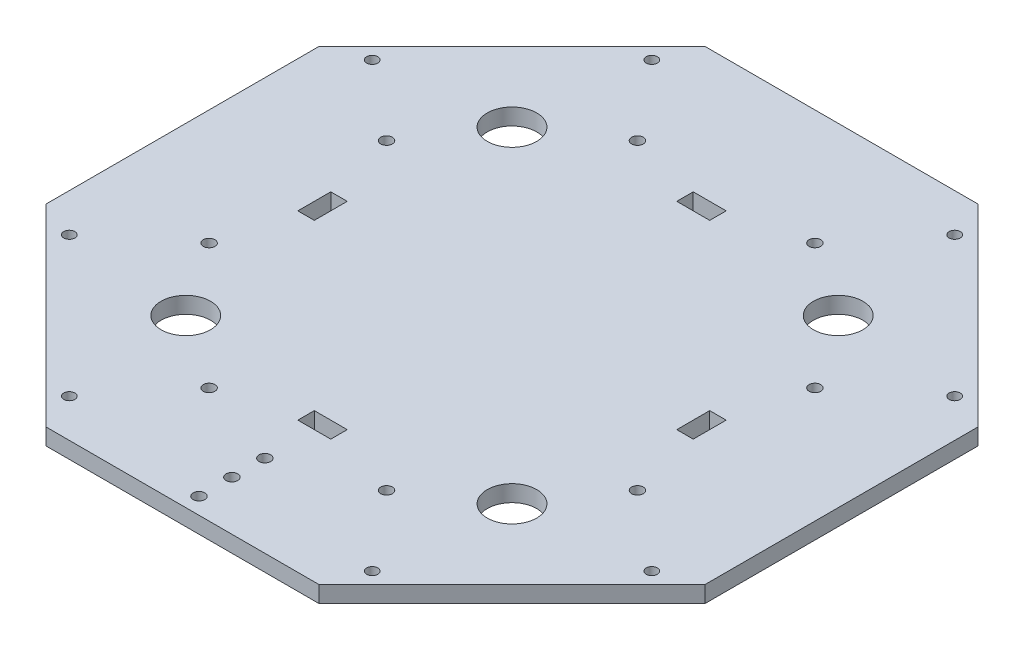
SolidWorks part; units mm, degrees
material "Custom Plastic"
ref_plane "Front Plane" through (0, 0, 0) normal (0, 0, 1) x (1, 0, 0)
ref_plane "Top Plane" through (0, 0, 0) normal (0, 1, 0) x (1, 0, 0)
ref_plane "Right Plane" through (0, 0, 0) normal (1, 0, 0) x (0, 0, -1)
ref_axis "Axis1" through (0, -0.2997, 0) along (0, 1, 0)
sketch "Base sketch" plane through (0, 0, 0) normal (0, 1, 0) x (1, 0, 0)
  line L1 (-127, 52.6051) -> (-127, -52.6051)
  line L2 (-127, -52.6051) -> (-52.6051, -127)
  line L3 (-52.6051, -127) -> (52.6051, -127)
  line L4 (52.6051, -127) -> (127, -52.6051)
  line L5 (127, -52.6051) -> (127, 52.6051)
  line L6 (127, 52.6051) -> (52.6051, 127)
  line L7 (52.6051, 127) -> (-52.6051, 127)
  line L8 (-52.6051, 127) -> (-127, 52.6051)
  circle A0 centre (0, 0) radius 127 construction
  dimension "D1" = 254
extrude "Base" add sketch "Base sketch" along normal blind 6.35
sketch "Sketch3" plane through (0, 6.35, 0) normal (0, 1, 0) x (1, 0, 0)
  line L0 (52.6051, 127) -> (-52.6051, 127) construction
  line L1 (-34.925, 114.3) -> (34.925, 114.3)
  line L2 (-34.925, 114.3) -> (-34.925, 79.375)
  line L4 (-34.925, 79.375) -> (34.925, 79.375)
  line L5 (34.925, 114.3) -> (34.925, 79.375)
  point P6 (0, 79.375)
  dimension "D1" = 69.85
  dimension "D2" = 34.925
  dimension "D3" = 12.7
sketch "Sketch4" plane through (0, 6.35, 0) normal (0, 1, 0) x (1, 0, 0)
  line L0 (0, 0) -> (0, 127) construction
  line L1 (52.6051, 127) -> (-52.6051, 127) construction
  line L4 (-6.35, 69.85) -> (6.35, 69.85)
  line L5 (-6.35, 69.85) -> (-6.35, 76.2)
  line L6 (-6.35, 76.2) -> (6.35, 76.2)
  line L7 (6.35, 69.85) -> (6.35, 76.2)
  line L8 (-6.35, 69.85) -> (6.35, 76.2) construction
  line L10 (-6.35, 76.2) -> (6.35, 69.85) construction
  point P5 (0, 73.025)
  dimension "D1" = 6.35
  dimension "D2" = 12.7
  dimension "D3" = 53.975
extrude "Support cutouts" cut sketch "Sketch4" against normal up to next
pattern_circular "Support cutout pattern" count 4 over 360 about axis through (0, -0.2997, 0) along (0, 1, 0) of "Support cutouts"
sketch "Sketch11" plane through (0, 6.35, 0) normal (0, 1, 0) x (1, 0, 0)
  line L1 (95.25, 39.4538) -> (39.4538, 95.25) construction
  line L2 (39.4538, 95.25) -> (-39.4538, 95.25) construction
  line L3 (-39.4538, 95.25) -> (-95.25, 39.4538) construction
  line L4 (-95.25, 39.4538) -> (-95.25, -39.4538) construction
  line L5 (-95.25, -39.4538) -> (-39.4538, -95.25) construction
  line L6 (-39.4538, -95.25) -> (39.4538, -95.25) construction
  line L7 (39.4538, -95.25) -> (95.25, -39.4538) construction
  line L8 (95.25, -39.4538) -> (95.25, 39.4538) construction
  line L9 (-34.1933, 82.55) -> (-82.55, 34.1933)
  line L10 (-82.55, 34.1933) -> (-82.55, -34.1933)
  line L11 (-82.55, -34.1933) -> (-34.1933, -82.55)
  line L12 (-34.1933, -82.55) -> (34.1933, -82.55)
  line L13 (34.1933, -82.55) -> (82.55, -34.1933)
  line L14 (82.55, -34.1933) -> (82.55, 34.1933)
  line L15 (82.55, 34.1933) -> (34.1933, 82.55)
  line L16 (34.1933, 82.55) -> (-34.1933, 82.55)
  circle A0 centre (0, 0) radius 95.25 construction
  circle A1 centre (0, 0) radius 82.55 construction
  dimension "D1" = 190.5
  dimension "D2" = 12.7
hole_wizard "#8 Clearance Hole1" positions "Sketch13" profile "Sketch12" hole size "#8" standard "ANSI Inch" end condition through all
sketch "Sketch13" plane through (0, 6.35, 0) normal (0, 1, 0) x (1, 0, 0)
  point P0 (-82.55, 34.1933)
  point P3 (-34.1933, 82.55)
  point P6 (34.1933, 82.55)
  point P9 (82.55, 34.1933)
  point P12 (82.55, -34.1933)
  point P15 (34.1933, -82.55)
  point P18 (-34.1933, -82.55)
  point P21 (-82.55, -34.1933)
sketch "Sketch12" plane through (-82.55, 6.35, -34.1933) normal (1, 0, 0) x (0, 0, 1)
  line L0 (0, 0) -> (0, 6.35)
  line L1 (0, 6.35) -> (2.2479, 6.35)
  line L2 (2.2479, 6.35) -> (2.2479, 0)
  line L5 (2.2479, 0) -> (0, 0)
  line L11 (0, -6.35) -> (0, 107.95) construction
  dimension "Thru Hole Dia." = 4.4958
  dimension "Thru Hole Depth" = 6.35
sketch "Sketch14" plane through (0, 6.35, 0) normal (0, 1, 0) x (1, 0, 0)
  circle A0 centre (-62.8618, 62.8618) radius 9.525
  circle A1 centre (62.8618, 62.8618) radius 9.525
  circle A2 centre (62.8618, -62.8618) radius 9.525
  circle A3 centre (-62.8618, -62.8618) radius 9.525
  point P13 (0, 0)
  dimension "D2" = 19.05
  dimension "D1" = 88.9
  dimension "D3" = 4
extrude "Cable holes" cut sketch "Sketch14" against normal up to next
sketch "Sketch15" plane through (0, 6.35, 0) normal (0, 1, 0) x (1, 0, 0)
  line L0 (0, -127) -> (0, 0) construction
  line L1 (-52.6051, -127) -> (52.6051, -127) construction
  point P5 (0, -120.65)
  point P6 (0, -107.95)
  point P7 (0, -95.25)
  dimension "D1" = 6.35
  dimension "D2" = 12.7
  dimension "D3" = 12.7
hole_wizard "#8 Clearance Hole2" positions "Sketch17" profile "Sketch16" hole size "#8" standard "ANSI Inch" end condition through all
sketch "Sketch17" plane through (0, 6.35, 0) normal (0, 1, 0) x (1, 0, 0)
  point P0 (0, -120.65)
  point P3 (0, -107.95)
  point P6 (0, -95.25)
sketch "Sketch16" plane through (0, 6.35, 120.65) normal (1, 0, 0) x (0, 0, 1)
  line L0 (0, 0) -> (0, 6.35)
  line L1 (0, 6.35) -> (2.2479, 6.35)
  line L2 (2.2479, 6.35) -> (2.2479, 0)
  line L5 (2.2479, 0) -> (0, 0)
  line L11 (0, -6.35) -> (0, 107.95) construction
  dimension "Thru Hole Dia." = 4.4958
  dimension "Thru Hole Depth" = 6.35
sketch "Sketch18" plane through (0, 6.35, 0) normal (0, 1, 0) x (1, 0, 0)
  line L0 (89.8026, 89.8026) -> (0, 0) construction
  line L1 (127, 52.6051) -> (52.6051, 127) construction
  line L2 (58.3717, 112.2532) -> (112.2532, 58.3717) construction
  point P7 (85.3124, 85.3124)
  dimension "D1" = 76.2
  dimension "D2" = 6.35
hole_wizard "plate mounting holes" positions "Sketch20" profile "Sketch19" hole size "#8" standard "ANSI Inch"
sketch "Sketch20" plane through (0, 6.35, 0) normal (0, 1, 0) x (1, 0, 0)
  point P0 (112.2532, 58.3717)
  point P7 (58.3717, 112.2532)
sketch "Sketch19" plane through (112.2532, 6.35, -58.3717) normal (1, 0, 0) x (0, 0, 1)
  line L0 (0, 0) -> (0, 6.351)
  line L1 (0, 6.351) -> (2.1526, 6.351)
  line L2 (2.1526, 6.351) -> (2.1526, 0)
  line L5 (2.1526, 0) -> (0, 0)
  line L10 (0, 6.351) -> (-2.1527, 6.351) construction
  line L11 (0, -6.35) -> (0, 107.95) construction
  dimension "Hole Dia." = 4.3053
  dimension "Hole Depth" = 6.351
  dimension "Drill Angle" = 180
pattern_circular "CirPattern1" count 4 over 360 about axis through (0, -0.2997, 0) along (0, 1, 0) of "plate mounting holes"
equation "\"MAT_THICKNESS\"=0.25"
equation "\"D1@Base\"=\"MAT_THICKNESS\""
equation "\"D1@Sketch4\"=\"MAT_THICKNESS\""
